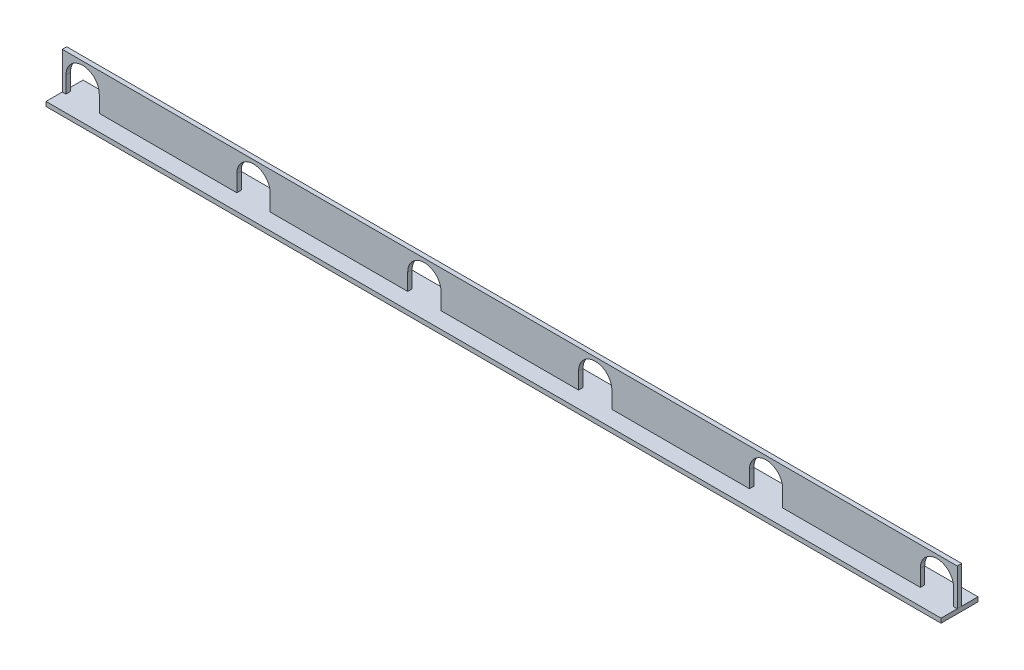
SolidWorks part; units mm, degrees
material "12Х18Н10Т ГОСТ 4543-71"
ref_plane "Спереди" through (0, 0, 0) normal (0, 0, 1) x (1, 0, 0)
ref_plane "Сверху" through (0, 0, 0) normal (0, 1, 0) x (1, 0, 0)
ref_plane "Справа" through (0, 0, 0) normal (1, 0, 0) x (0, 0, -1)
sketch "Эскиз1" plane through (0, 0, 0) normal (0, 0, 1) x (1, 0, 0)
  line L0 (-600, -2.5) -> (-600, -25)
  line L1 (-605, -25) -> (-600, -25)
  line L2 (-605, -25) -> (-605, 25)
  line L3 (-605, 25) -> (605, 25)
  line L4 (605, -25) -> (605, 25)
  line L5 (0, 25) -> (0, -25) construction
  line L6 (-605, 0) -> (605, 0) construction
  line L7 (-555, -2.5) -> (-555, -25)
  line L8 (-555, -25) -> (-369, -25)
  line L9 (-369, -2.5) -> (-369, -25)
  line L10 (-324, -2.5) -> (-324, -25)
  line L11 (-138, -2.5) -> (-138, -25)
  line L12 (-93, -2.5) -> (-93, -25)
  line L13 (93, -2.5) -> (93, -25)
  line L14 (138, -2.5) -> (138, -25)
  line L15 (324, -2.5) -> (324, -25)
  line L16 (369, -2.5) -> (369, -25)
  line L17 (555, -2.5) -> (555, -25)
  line L18 (600, -2.5) -> (600, -25)
  line L19 (-324, -25) -> (-138, -25)
  line L20 (-93, -25) -> (93, -25)
  line L21 (138, -25) -> (324, -25)
  line L22 (369, -25) -> (555, -25)
  line L23 (600, -25) -> (605, -25)
  arc A0 (-555, -2.5) -> (-600, -2.5) centre (-577.5, -2.5) ccw
  arc A1 (-324, -2.5) -> (-369, -2.5) centre (-346.5, -2.5) ccw
  arc A2 (-93, -2.5) -> (-138, -2.5) centre (-115.5, -2.5) ccw
  arc A3 (138, -2.5) -> (93, -2.5) centre (115.5, -2.5) ccw
  arc A4 (369, -2.5) -> (324, -2.5) centre (346.5, -2.5) ccw
  arc A5 (600, -2.5) -> (555, -2.5) centre (577.5, -2.5) ccw
  point P0 (0, 0)
  dimension "D3" = 45
  dimension "D1" = 1210
  dimension "D2" = 50
  dimension "D5" = 5
  dimension "D4" = 6
extrude "Бобышка-Вытянуть1" add sketch "Эскиз1" along normal mid plane 6
sketch "Эскиз2" plane through (0, -25, 0) normal (0, -1, 0) x (1, 0, 0)
  line L0 (605, 3) -> (605, -3) construction
  line L1 (-605, -25) -> (605, -25)
  line L2 (-605, -25) -> (-605, 25)
  line L3 (-605, 25) -> (605, 25)
  line L4 (605, -25) -> (605, 25)
  line L5 (0, 25) -> (0, -25) construction
  line L6 (-605, 0) -> (605, 0) construction
  point P0 (0, 0)
  point P4 (0, 0)
  point P5 (0, 0)
  dimension "D1" = 50
extrude "Бобышка-Вытянуть2" add sketch "Эскиз2" along normal blind 6 separate body
